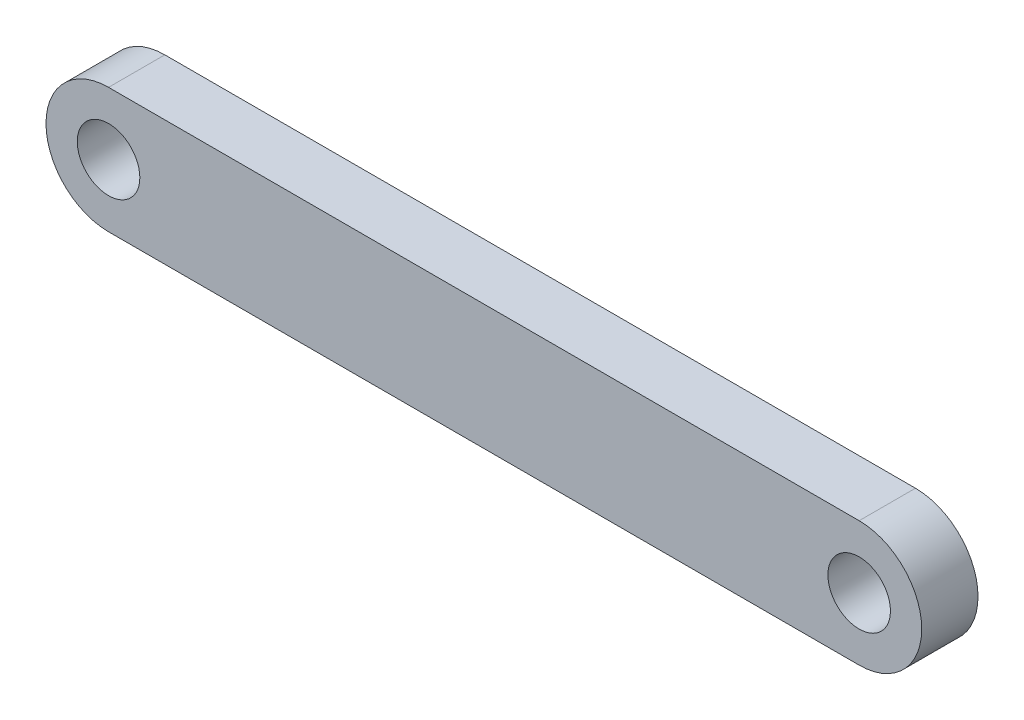
SolidWorks part; units mm, degrees
ref_plane "Front Plane" through (0, 0, 0) normal (0, 0, 1) x (1, 0, 0)
ref_plane "Top Plane" through (0, 0, 0) normal (0, 1, 0) x (1, 0, 0)
ref_plane "Right Plane" through (0, 0, 0) normal (1, 0, 0) x (0, 0, -1)
ref_axis "X" through (-88.99, 0, 0) along (1, 0, 0)
ref_axis "Y" through (0, 55, 0) along (0, -1, 0)
ref_axis "Z" through (0, 0, -88.99) along (0, 0, 1)
sketch "Sketch1" plane through (0, 0, 0) normal (0, 0, 1) x (1, 0, 0)
  line L0 (-60, 0) -> (60, 0) construction
  line L1 (-60, 10) -> (60, 10)
  line L2 (-60, -10) -> (60, -10)
  arc A0 (-60, 10) -> (-60, -10) centre (-60, 0) ccw
  arc A1 (60, -10) -> (60, 10) centre (60, 0) ccw
  circle A2 centre (-60, 0) radius 5
  circle A3 centre (60, 0) radius 5
  point P2 (0, 0)
  dimension "D1" = 5
  dimension "D3" = 10
  dimension "D2" = 120
extrude "Boss-Extrude1" add sketch "Sketch1" along normal mid plane 9
